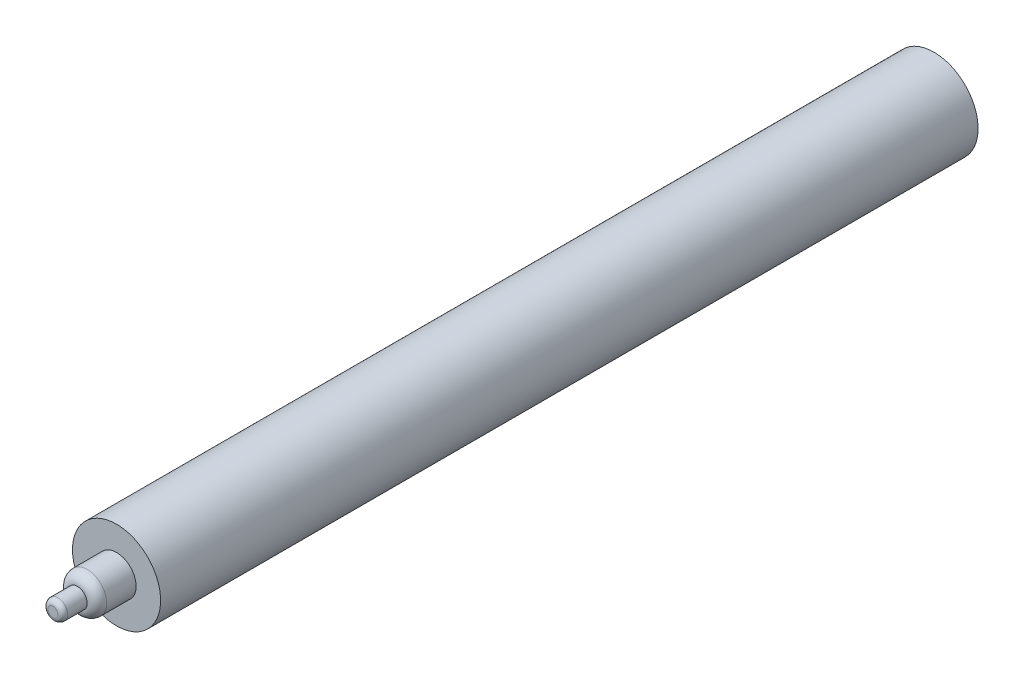
SolidWorks part; units mm, degrees
ref_plane "Спереди" through (0, 0, 0) normal (0, 0, 1) x (1, 0, 0)
ref_plane "Сверху" through (0, 0, 0) normal (0, 1, 0) x (1, 0, 0)
ref_plane "Справа" through (0, 0, 0) normal (1, 0, 0) x (0, 0, -1)
sketch "Эскиз1" plane through (0, 0, 0) normal (0, 0, 1) x (1, 0, 0)
  circle A0 centre (0, 0) radius 9
  dimension "D1" = 18
extrude "Бобышка-Вытянуть1" add sketch "Эскиз1" along normal blind 167
sketch "Эскиз2" plane through (0, 0, 167) normal (0, 0, 1) x (1, 0, 0)
  circle A0 centre (0, 0) radius 4
  dimension "D1" = 8
extrude "Бобышка-Вытянуть2" add sketch "Эскиз2" along normal blind 8
sketch "Эскиз3" plane through (0, 0, 175) normal (0, 0, 1) x (1, 0, 0)
  circle A0 centre (0, 0) radius 2
  dimension "D1" = 4
extrude "Бобышка-Вытянуть3" add sketch "Эскиз3" along normal blind 5
fillet "Скругление1" radius 2 1 edges at (4, 0, 175)
fillet "Скругление2" radius 1 1 edges at (2, 0, 180)
